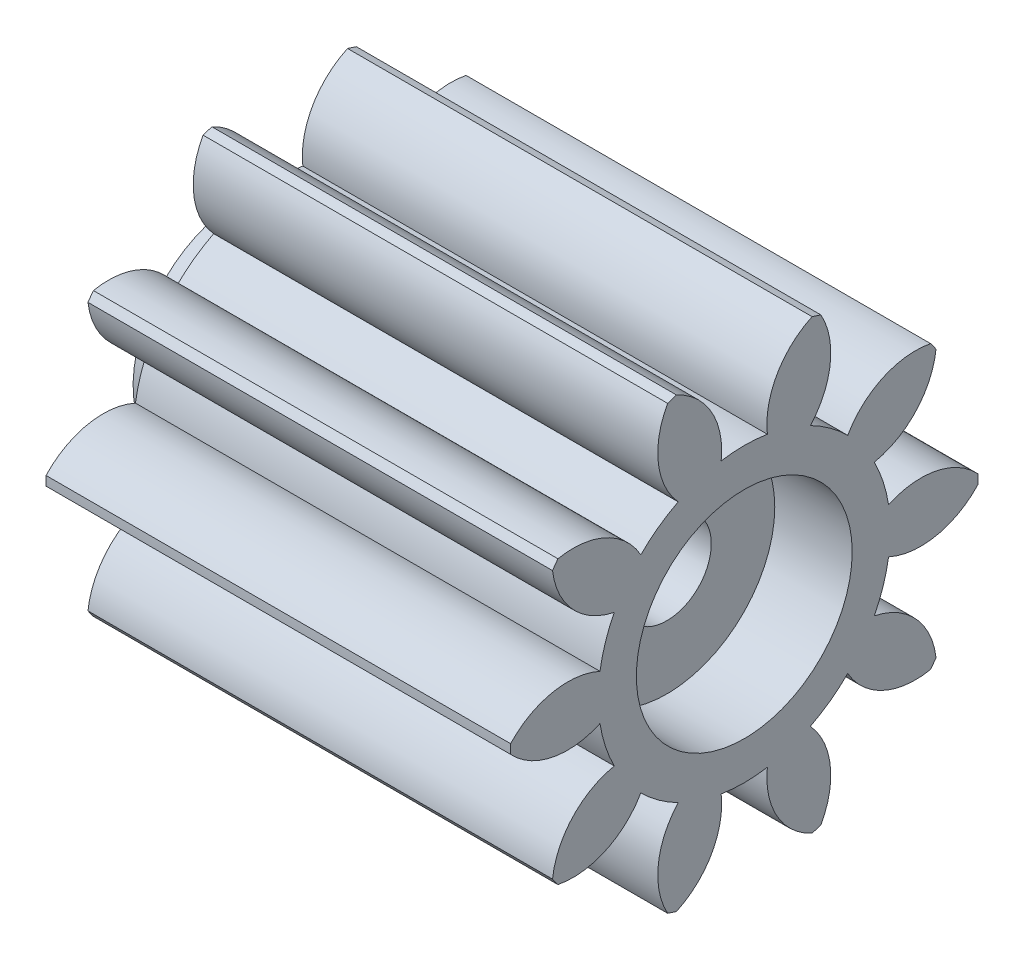
SolidWorks part; units mm, degrees
ref_plane "Front Plane" through (0, 0, 0) normal (0, 0, 1) x (1, 0, 0)
ref_plane "Top Plane" through (0, 0, 0) normal (0, 1, 0) x (1, 0, 0)
ref_plane "Right Plane" through (0, 0, 0) normal (1, 0, 0) x (0, 0, -1)
sketch "Sketch1" plane through (0, 0, 0) normal (1, 0, 0) x (0, 0, -1)
  circle A0 centre (0, 0) radius 1.4
  arc A1 (7.3616, 0.1459) -> (4.5452, 0.712) centre (5.5612, -1.5222) ccw
  arc A2 (4.5452, 0.712) -> (4.0957, 2.0956) centre (0, 0) ccw
  arc A3 (4.0957, 2.0956) -> (6.0414, 4.209) centre (3.6044, 4.5003) ccw
  arc A4 (6.0414, 4.209) -> (5.8699, 4.4451) centre (0, 0) ccw
  arc A5 (5.8699, 4.4451) -> (3.2587, 3.2476) centre (5.3939, 2.0373) ccw
  arc A6 (3.2587, 3.2476) -> (2.0817, 4.1028) centre (0, 0) ccw
  arc A7 (2.0817, 4.1028) -> (2.4136, 6.9562) centre (0.2708, 5.7595) ccw
  arc A8 (2.4136, 6.9562) -> (2.1361, 7.0464) centre (0, 0) ccw
  arc A9 (2.1361, 7.0464) -> (0.7274, 4.5428) centre (3.1662, 4.8187) ccw
  arc A10 (0.7274, 4.5428) -> (-0.7274, 4.5428) centre (0, 0) ccw
  arc A11 (-0.7274, 4.5428) -> (-2.1361, 7.0464) centre (-3.1662, 4.8187) ccw
  arc A12 (-2.1361, 7.0464) -> (-2.4136, 6.9562) centre (0, 0) ccw
  arc A13 (-2.4136, 6.9562) -> (-2.0817, 4.1028) centre (-0.2708, 5.7595) ccw
  arc A14 (-2.0817, 4.1028) -> (-3.2587, 3.2476) centre (0, 0) ccw
  arc A15 (-3.2587, 3.2476) -> (-5.8699, 4.4451) centre (-5.3939, 2.0373) ccw
  arc A16 (-5.8699, 4.4451) -> (-6.0414, 4.209) centre (0, 0) ccw
  arc A17 (-6.0414, 4.209) -> (-4.0957, 2.0956) centre (-3.6044, 4.5003) ccw
  arc A18 (-4.0957, 2.0956) -> (-4.5452, 0.712) centre (0, 0) ccw
  arc A19 (-4.5452, 0.712) -> (-7.3616, 0.1459) centre (-5.5612, -1.5222) ccw
  arc A20 (-7.3616, 0.1459) -> (-7.3616, -0.1459) centre (0, 0) ccw
  arc A21 (-7.3616, -0.1459) -> (-4.5452, -0.712) centre (-5.5612, 1.5222) ccw
  arc A22 (-4.5452, -0.712) -> (-4.0957, -2.0956) centre (0, 0) ccw
  arc A23 (-4.0957, -2.0956) -> (-6.0414, -4.209) centre (-3.6044, -4.5003) ccw
  arc A24 (-6.0414, -4.209) -> (-5.8699, -4.4451) centre (0, 0) ccw
  arc A25 (-5.8699, -4.4451) -> (-3.2587, -3.2476) centre (-5.3939, -2.0373) ccw
  arc A26 (-3.2587, -3.2476) -> (-2.0817, -4.1028) centre (0, 0) ccw
  arc A27 (-2.0817, -4.1028) -> (-2.4136, -6.9562) centre (-0.2708, -5.7595) ccw
  arc A28 (-2.4136, -6.9562) -> (-2.1361, -7.0464) centre (0, 0) ccw
  arc A29 (-2.1361, -7.0464) -> (-0.7274, -4.5428) centre (-3.1662, -4.8187) ccw
  arc A30 (-0.7274, -4.5428) -> (0.7274, -4.5428) centre (0, 0) ccw
  arc A31 (0.7274, -4.5428) -> (2.1361, -7.0464) centre (3.1662, -4.8187) ccw
  arc A32 (2.1361, -7.0464) -> (2.4136, -6.9562) centre (0, 0) ccw
  arc A33 (2.4136, -6.9562) -> (2.0817, -4.1028) centre (0.2708, -5.7595) ccw
  arc A34 (2.0817, -4.1028) -> (3.2587, -3.2476) centre (0, 0) ccw
  arc A35 (3.2587, -3.2476) -> (5.8699, -4.4451) centre (5.3939, -2.0373) ccw
  arc A36 (5.8699, -4.4451) -> (6.0414, -4.209) centre (0, 0) ccw
  arc A37 (6.0414, -4.209) -> (4.0957, -2.0956) centre (3.6044, -4.5003) ccw
  arc A38 (4.0957, -2.0956) -> (4.5452, -0.712) centre (0, 0) ccw
  arc A39 (4.5452, -0.712) -> (7.3616, -0.1459) centre (5.5612, 1.5222) ccw
  arc A40 (7.3616, -0.1459) -> (7.3616, 0.1459) centre (0, 0) ccw
  circle A41 centre (0, 0) radius 3.4
  point P63 (0, 0)
  dimension "D1" = 2.8
  dimension "D2" = 2
extrude "Boss-Extrude1" add sketch "Sketch1" against normal mid plane 12 contours A39 A40 A1 A2 A3 A4 A5 A6 A7 A8 A9 A10 A11 A12 A13 A14 A15 A16 A17 A18 A19 A20 A21 A22 A23 A24 A25 A26 A27 A28 A29 A30 A31 A32 A33 A34 A35 A36 A37 A38 A41 region at (0, 0, -7.1592)
extrude "Boss-Extrude2" add sketch "Sketch1<4>" along normal offset from surface 2 and the other way blind 7 contours A41 A0 region at (0, 0, 3.3038) up to face at (6, 0, -3.4)
sketch "Sketch1<4>" plane through (0, 0, 0) normal (1, 0, 0) x (0, 0, -1) same geometry as "Sketch1"
scale "Scale1" scale about centroid uniform scaling no x scale factor 1 y scale factor 0.82 z scale factor 0.82
